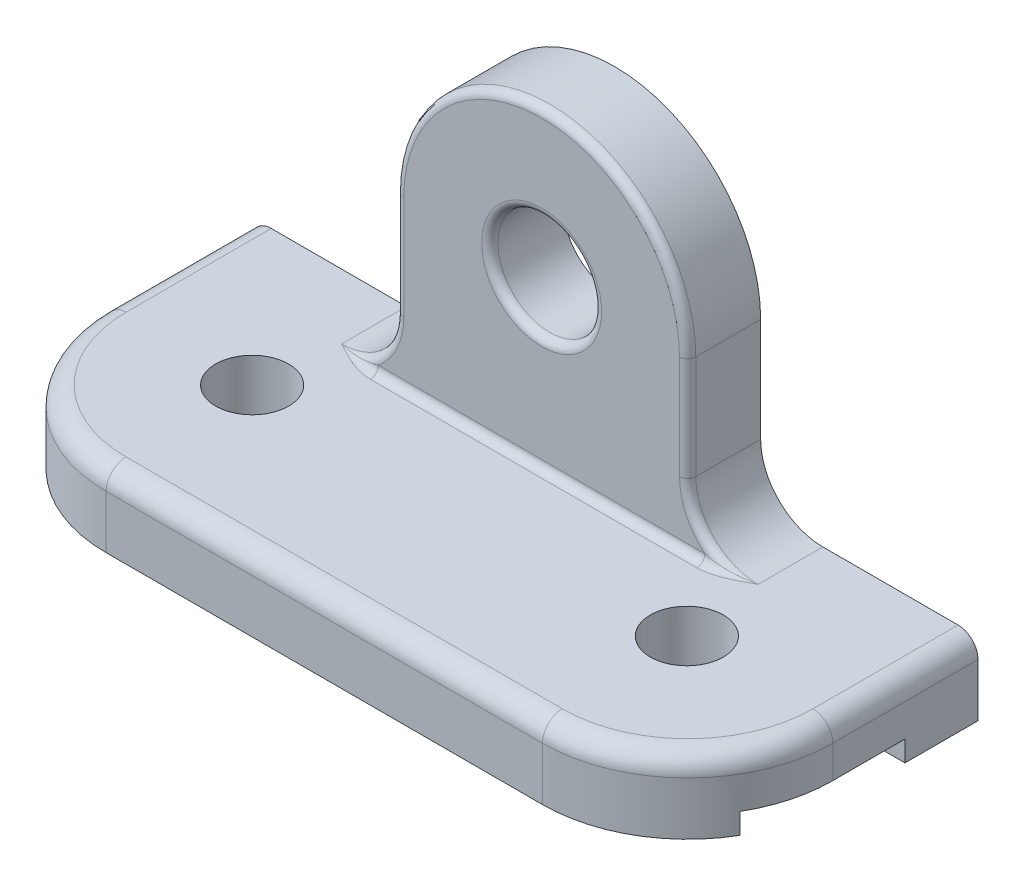
SolidWorks part; units mm, degrees
ref_plane "Front Plane" through (0, 0, 0) normal (0, 0, 1) x (1, 0, 0)
ref_plane "Top Plane" through (0, 0, 0) normal (0, 1, 0) x (1, 0, 0)
ref_plane "Right Plane" through (0, 0, 0) normal (1, 0, 0) x (0, 0, -1)
sketch "Sketch2" plane through (0, 0, 0) normal (0, 1, 0) x (1, 0, 0)
  line L0 (-55.626, 0) -> (55.626, 0)
  line L1 (-55, 0) -> (55, 0) construction
  line L2 (55.626, 0) -> (55.626, -22.225)
  line L3 (33.401, -44.45) -> (-33.401, -44.45)
  line L4 (-55.626, -22.225) -> (-55.626, 0)
  line L5 (0, -55) -> (0, 55) construction
  arc A0 (-33.401, -44.45) -> (-55.626, -22.225) centre (-33.401, -22.225) cw
  arc A1 (55.626, -22.225) -> (33.401, -44.45) centre (33.401, -22.225) cw
  dimension "D4" = 22.225
  dimension "D5" = 22.225
  dimension "D1" = 111.252
  dimension "D2" = 55.626
  dimension "D3" = 44.45
extrude "Boss-Extrude1" add sketch "Sketch2" along normal blind 11.176
sketch "Sketch3" plane through (0, 0, 0) normal (0, 0, 1) x (1, 0, 0)
  line L0 (-22.352, 36.576) -> (-22.352, 11.176)
  line L1 (-33.401, 11.176) -> (33.401, 11.176) construction
  line L2 (22.352, 36.576) -> (22.352, 11.176)
  line L3 (-22.352, 11.176) -> (22.352, 11.176)
  arc A0 (22.352, 36.576) -> (-22.352, 36.576) centre (0, 36.576) ccw
  circle A1 centre (0, 36.576) radius 7.9375
  dimension "D1" = 22.352
  dimension "D2" = 15.875
  dimension "D3" = 36.576
extrude "Boss-Extrude2" add sketch "Sketch3" along normal blind 11.176
fillet "Fillet1" radius 9.525 2 edges at (-22.352, 11.176, 5.588) (22.352, 11.176, 5.588)
fillet "Fillet2" radius 1.2446 7 edges at (7.9375, 36.576, 11.176) (22.352, 28.6385, 11.176) (25.1418, 13.9658, 11.176) (0, 11.176, 11.176) (-25.1418, 13.9658, 11.176) (-22.352, 28.6385, 11.176) (0, 58.928, 11.176)
fillet "Fillet3" radius 3.048 5 edges at (55.626, 11.176, 11.1125) (49.1164, 11.176, 37.9404) (0, 11.176, 44.45) (-49.1164, 11.176, 37.9404) (-55.626, 11.176, 11.1125)
sketch "Sketch4" plane through (0, 0, 0) normal (1, 0, 0) x (0, 0, -1)
  line L0 (-33.401, 0) -> (-11.176, 0)
  line L1 (24.4475, 0) -> (-24.4475, 0) construction
  line L2 (-11.176, 0) -> (-11.176, 3.175)
  line L3 (-11.176, 3.175) -> (-33.401, 3.175)
  line L4 (-33.401, 3.175) -> (-33.401, 0)
  line L5 (0, 32.4104) -> (0, -32.4104) construction
  dimension "D1" = 22.225
  dimension "D2" = 3.175
  dimension "D3" = 11.176
extrude "Cut-Extrude1" cut sketch "Sketch4" against normal through all both and the other way through all
sketch "Sketch5" plane through (0, 0, 0) normal (0, 1, 0) x (1, 0, 0)
  line L0 (0, -24.4475) -> (0, 24.4475) construction
  line L1 (-32.4104, 0) -> (32.4104, 0) construction
  circle A0 centre (-33.274, -22.225) radius 5.588
  dimension "D1" = 11.176
  dimension "D2" = 33.274
  dimension "D3" = 22.225
extrude "Cut-Extrude3" cut sketch "Sketch5" along normal up to next and the other way through all
mirror "Mirror1" about plane through (0, 0, 0) normal (1, 0, 0) of "Cut-Extrude3"
